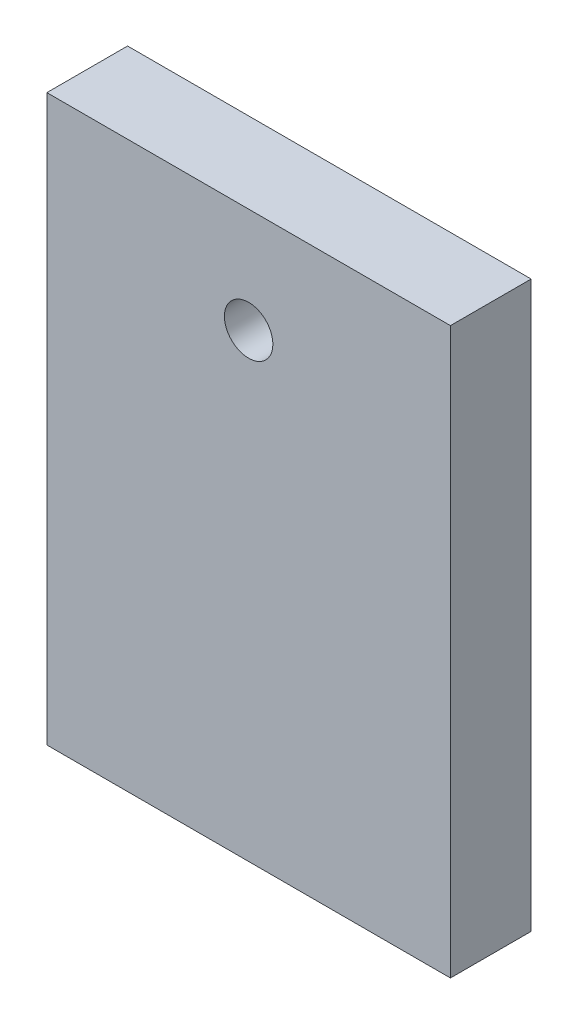
SolidWorks part; units mm, degrees
ref_plane "Front Plane" through (0, 0, 0) normal (0, 0, 1) x (1, 0, 0)
ref_plane "Top Plane" through (0, 0, 0) normal (0, 1, 0) x (1, 0, 0)
ref_plane "Right Plane" through (0, 0, 0) normal (1, 0, 0) x (0, 0, -1)
sketch "Sketch2" plane through (0, 0, 0) normal (0, 0, 1) x (1, 0, 0)
  line L1 (-12.5, -17.5) -> (12.5, -17.5)
  line L2 (-12.5, -17.5) -> (-12.5, 17.5)
  line L3 (-12.5, 17.5) -> (12.5, 17.5)
  line L4 (12.5, -17.5) -> (12.5, 17.5)
  line L5 (-12.5, -17.5) -> (12.5, 17.5) construction
  line L6 (-12.5, 17.5) -> (12.5, -17.5) construction
  point P0 (0, 0)
  dimension "D1" = 25
  dimension "D2" = 35
extrude "Boss-Extrude1" add sketch "Sketch2" along normal blind 5
sketch "Sketch4" plane through (0, 0, 5) normal (0, 0, 1) x (1, 0, 0)
  line L0 (0, -17.5) -> (0, -7.5) construction
  line L1 (-12.5, -17.5) -> (12.5, -17.5) construction
  line L2 (0, -7.5) -> (0, 11) construction
  circle A0 centre (0, 11) radius 1.5
  dimension "D3" = 3
  dimension "D1" = 10
  dimension "D2" = 18.5
extrude "Cut-Extrude1" cut sketch "Sketch4" against normal through all
